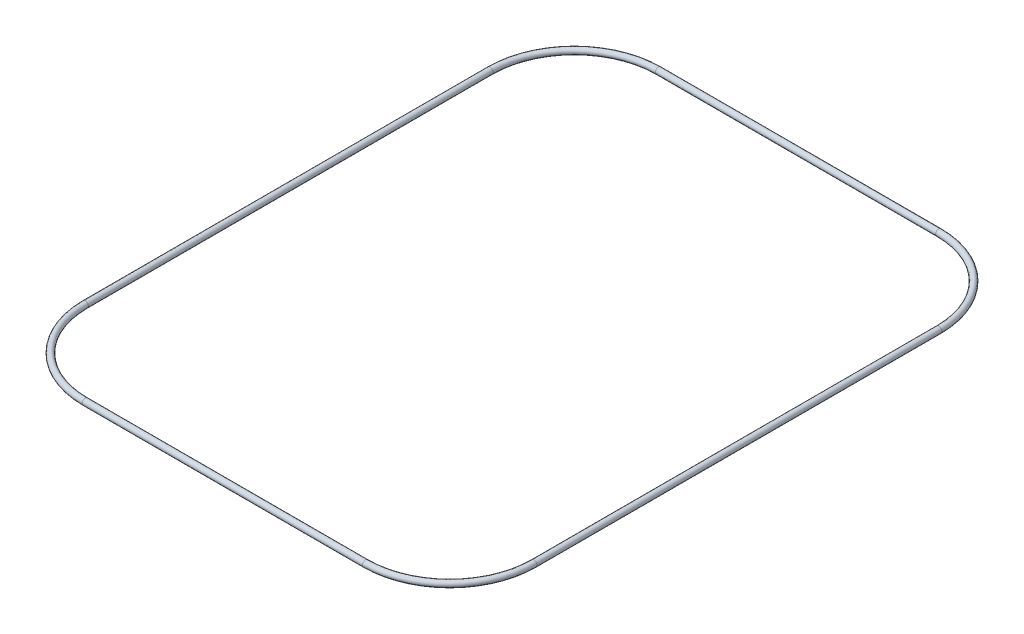
SolidWorks part; units mm, degrees
ref_plane "Front" through (0, 0, 0) normal (0, 0, 1) x (1, 0, 0)
ref_plane "Top" through (0, 0, 0) normal (0, 1, 0) x (1, 0, 0)
ref_plane "Right" through (0, 0, 0) normal (1, 0, 0) x (0, 0, -1)
ref_axis "X Axis" through (-86.0983, 0, 0) along (1, 0, 0)
ref_axis "Y Axis" through (0, -1.0897, 0) along (0, 1, 0)
ref_axis "Z Axis" through (0, 0, 96.2236) along (0, 0, -1)
sketch "Sketch1" plane through (0, 0, 0) normal (0, 1, 0) x (1, 0, 0)
  line L4 (66.2758, -58.8898) -> (66.2758, 71.1102)
  line L5 (39.2356, 98.1504) -> (-50.7644, 98.1504)
  line L6 (-77.8046, 71.1102) -> (-77.8046, -58.8898)
  line L7 (-50.7644, -85.93) -> (39.2356, -85.93)
  arc A4 (66.2758, 71.1102) -> (39.2356, 98.1504) centre (39.2356, 71.1102) ccw
  arc A5 (-50.7644, 98.1504) -> (-77.8046, 71.1102) centre (-50.7644, 71.1102) ccw
  arc A6 (-77.8046, -58.8898) -> (-50.7644, -85.93) centre (-50.7644, -58.8898) ccw
  arc A7 (39.2356, -85.93) -> (66.2758, -58.8898) centre (39.2356, -58.8898) ccw
ref_plane "Plane1" through (66.2758, 0, -71.1102) normal (0, 0, -1) x (-1, 0, 0)
sketch "Sketch2" plane through (66.2758, 0, -71.1102) normal (0, 0, -1) x (-1, 0, 0)
  circle A0 centre (0, 0) radius 0.9906
  dimension "D1" = 1.9812
sweep "Sweep1" add profiles "Sketch2" path "Sketch1"
